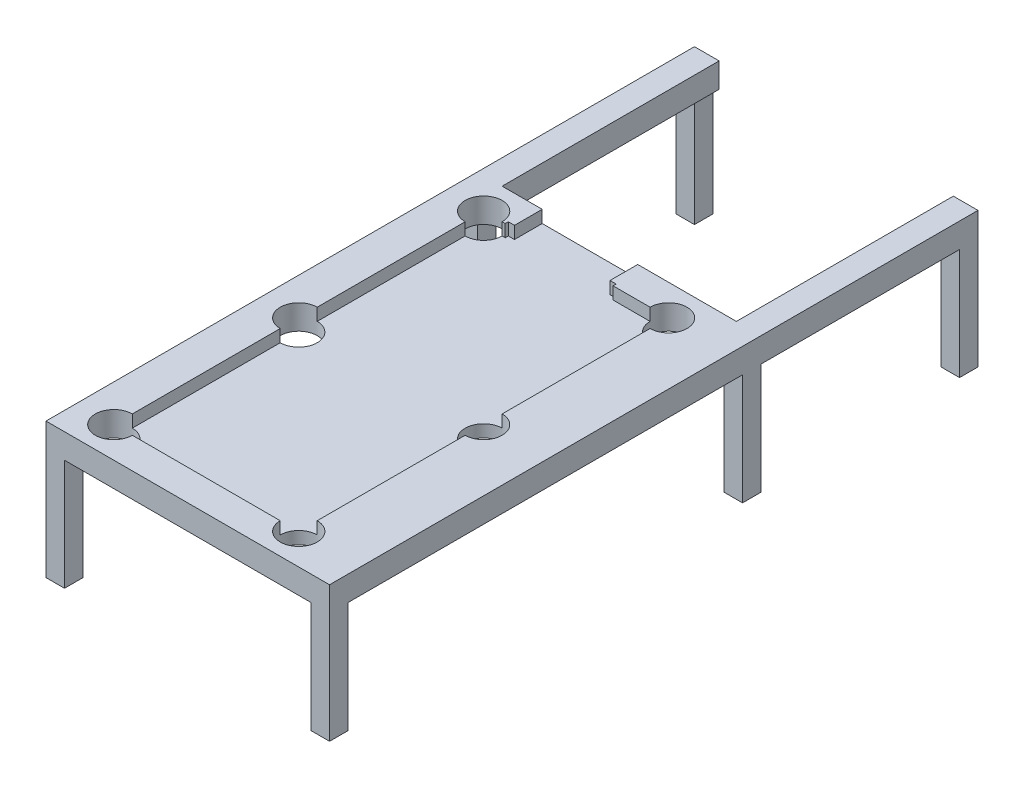
SolidWorks part; units mm, degrees
ref_plane "Front Plane" through (0, 0, 0) normal (0, 0, 1) x (1, 0, 0)
ref_plane "Top Plane" through (0, 0, 0) normal (0, 1, 0) x (1, 0, 0)
ref_plane "Right Plane" through (0, 0, 0) normal (1, 0, 0) x (0, 0, -1)
sketch "Sketch2" plane through (0, 0, 0) normal (0, 1, 0) x (1, 0, 0)
  line L1 (0, 0) -> (460, 0)
  line L2 (0, 0) -> (0, 700)
  line L3 (0, 700) -> (460, 700)
  line L4 (460, 0) -> (460, 700)
  line L5 (60, 50) -> (360, 50)
  line L6 (60, 50) -> (60, 650)
  line L7 (60, 650) -> (360, 650)
  line L8 (360, 50) -> (360, 650)
  dimension "D1" = 700
  dimension "D2" = 460
  dimension "D3" = 600
  dimension "D4" = 300
  dimension "D5" = 60
  dimension "D6" = 50
extrude "Boss-Extrude1" add sketch "Sketch2" along normal blind 20
ref_plane "Plane1" through (0, 0, -700) normal (0, 0, -1) x (-1, 0, 0)
sketch "Sketch10" plane through (0, 0, 0) normal (0, -1, 0) x (1, 0, 0)
  line L1 (0, 0) -> (460, 0)
  line L2 (0, 0) -> (0, -700)
  line L3 (0, -700) -> (460, -700)
  line L4 (460, 0) -> (460, -700)
extrude "Boss-Extrude6" add sketch "Sketch10" along normal blind 20
sketch "Sketch11" plane through (0, -20, 0) normal (0, -1, 0) x (1, 0, 0)
  line L1 (0, 0) -> (30, 0)
  line L2 (0, 0) -> (0, -30)
  line L3 (0, -30) -> (30, -30)
  line L4 (30, 0) -> (30, -30)
  line L5 (460, 0) -> (430, 0)
  line L6 (460, 0) -> (460, -30)
  line L7 (460, -30) -> (430, -30)
  line L8 (430, 0) -> (430, -30)
  line L9 (0, -700) -> (30, -700)
  line L10 (0, -700) -> (0, -670)
  line L11 (0, -670) -> (30, -670)
  line L12 (30, -700) -> (30, -670)
  line L13 (460, -700) -> (430, -700)
  line L14 (460, -700) -> (460, -670)
  line L15 (460, -670) -> (430, -670)
  line L16 (430, -700) -> (430, -670)
  dimension "D1" = 30
extrude "Boss-Extrude7" add sketch "Sketch11" along normal blind 180
sketch "Sketch14" plane through (0, 20, 0) normal (0, 1, 0) x (1, 0, 0)
  line L0 (22, 700) -> (-22, 700) construction
  line L1 (0, 700) -> (40, 700)
  line L2 (0, 700) -> (0, 1052)
  line L3 (0, 1052) -> (40, 1052)
  line L4 (40, 700) -> (40, 1052)
  line L5 (0, 700) -> (0, 0) construction
  line L6 (460, 0) -> (460, 700) construction
  line L7 (460, 700) -> (420, 700)
  line L8 (460, 700) -> (460, 1052)
  line L9 (460, 1052) -> (420, 1052)
  line L10 (420, 700) -> (420, 1052)
  line L11 (330, 1052) -> (390, 1052) construction
  dimension "D3" = 40
  dimension "D4" = 40
extrude "Boss-Extrude8" add sketch "Sketch14" against normal blind 40
sketch "Sketch15" plane through (0, -20, 0) normal (0, -1, 0) x (1, 0, 0)
  line L1 (460, -1052) -> (430, -1052)
  line L2 (460, -1052) -> (460, -1022)
  line L3 (460, -1022) -> (430, -1022)
  line L4 (430, -1052) -> (430, -1022)
  line L6 (0, -1052) -> (30, -1052)
  line L7 (0, -1052) -> (0, -1022)
  line L8 (0, -1022) -> (30, -1022)
  line L9 (30, -1052) -> (30, -1022)
  dimension "D1" = 30
  dimension "D2" = 30
  dimension "D3" = 30
  dimension "D4" = 30
extrude "Boss-Extrude9" add sketch "Sketch15" along normal blind 180
sketch "Sketch17" plane through (0, 20, 0) normal (0, 1, 0) x (1, 0, 0)
  line L0 (60, 650) -> (60, 50) construction
  line L1 (360, 50) -> (360, 650) construction
  circle A0 centre (60, 650) radius 30
  circle A1 centre (60, 350) radius 30
  circle A2 centre (60, 50) radius 30
  circle A3 centre (360, 50) radius 30
  circle A4 centre (360, 350) radius 30
  circle A5 centre (360, 650) radius 30
  line M15 (60, 50) -> (60, 650)
  line M16 (60, 650) -> (360, 650)
  line M17 (360, 650) -> (360, 50)
  line M18 (360, 50) -> (60, 50)
  dimension "D1" = 60
extrude "Cut-Extrude1" cut sketch "Sketch17" against normal blind 60 contours A5 M17 M16 | A4 M17 | A3 M18 M17 | A1 M15 | A1 M15 | A2 M15 M18 | A2 M18 M15 | A3 M17 M18 | A5 M16 M17 | A4 M17 | A0 region at (347.2676, 20, -637.2676) region at (364.2441, 20, -654.2441) region at (47.2676, 20, -350) region at (72.7324, 20, -350) region at (347.2676, 20, -350) region at (372.7324, 20, -350) region at (55.7559, 20, -45.7559) region at (72.7324, 20, -62.7324) region at (347.2676, 20, -62.7324) region at (364.2441, 20, -45.7559)
sketch "Sketch18" plane through (0, 20, 0) normal (0, 1, 0) x (1, 0, 0)
  line L3 (260, 650) -> (270, 650)
  line L9 (330, 650) -> (90, 650) construction
  line L10 (420, 700) -> (40, 700) construction
  line L11 (182.5, 700) -> (260, 700)
  line L12 (260, 700) -> (260, 650)
  line L13 (330, 650) -> (90, 650) construction
  line L14 (210, 650) -> (260, 650)
  line L15 (182.5, 700) -> (105, 700)
  line L16 (105, 700) -> (105, 650)
  line L17 (105, 650) -> (210, 650)
  line L18 (260, 650) -> (260, 655)
  line L19 (260, 655) -> (270, 655)
  line L20 (270, 650) -> (270, 655)
  line L21 (105, 650) -> (95, 650)
  line L22 (105, 650) -> (105, 655)
  line L23 (105, 655) -> (95, 655)
  line L24 (95, 650) -> (95, 655)
  line M17 (420, 700) -> (40, 700)
  line M26 (90, 650) -> (330, 650)
  dimension "D1" = 77.5
  dimension "D2" = 77.5
  dimension "D3" = 70
  dimension "D4" = 10
  dimension "D5" = 5
extrude "Cut-Extrude2" cut sketch "Sketch18" against normal blind 20 contours L24 L16 L23 M26 | L16 L12 M17 M26 | L20 L19 L12 M26 region at (265, 20, -652.5) region at (182.5, 20, -675) region at (100, 20, -652.5)
sketch "Sketch19" plane through (95, 0, 0) normal (1, 0, 0) x (0, 0, -1)
  line L0 (650, 0) -> (652.5, 0) construction
  line L1 (650, 0) -> (655, 0) construction
  line L2 (652.5, 0) -> (652.5, 2.5) construction
  point P8 (652.5, 2.5)
  dimension "D1" = 2.5
